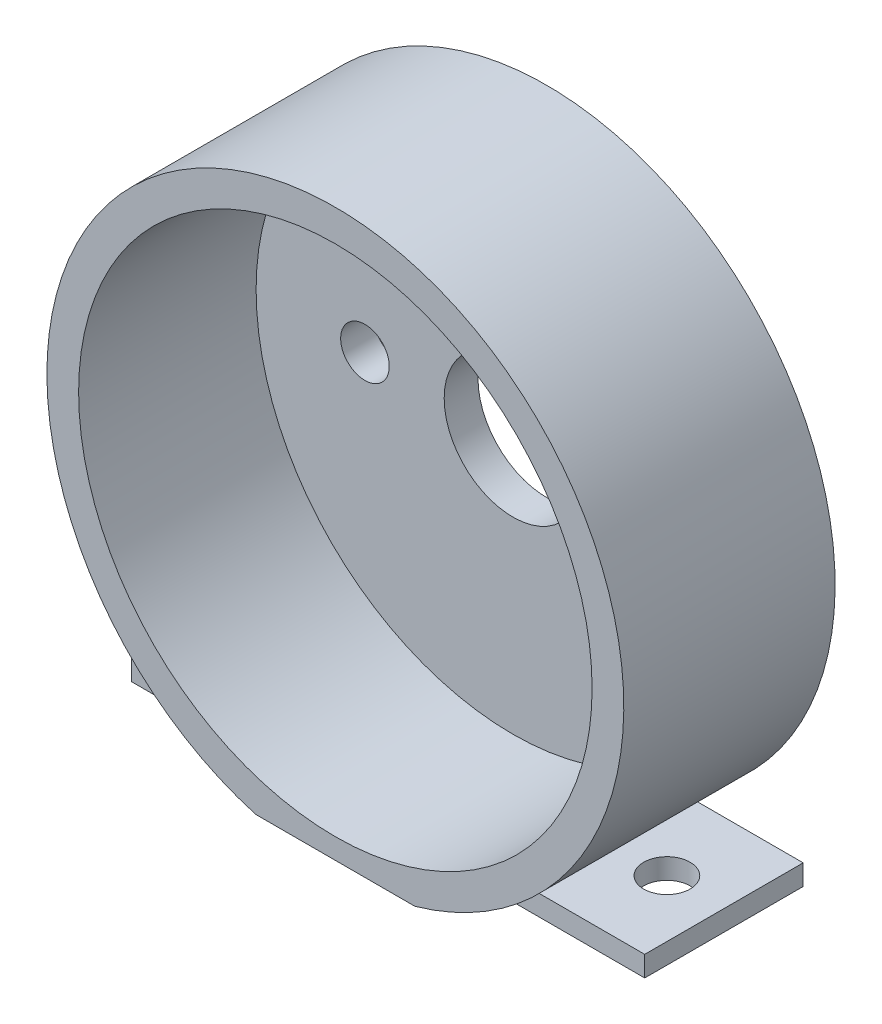
SolidWorks part; units mm, degrees
ref_plane "Front Plane" through (0, 0, 0) normal (0, 0, 1) x (1, 0, 0)
ref_plane "Top Plane" through (0, 0, 0) normal (0, 1, 0) x (1, 0, 0)
ref_plane "Right Plane" through (0, 0, 0) normal (1, 0, 0) x (0, 0, -1)
sketch "Sketch1" plane through (0, 0, 0) normal (0, 0, 1) x (1, 0, 0)
  circle A0 centre (0, 0) radius 12.15
  circle A1 centre (0, 0) radius 13.65
extrude "Boss-Extrude1" add sketch "Sketch1" along normal blind 10
sketch "Sketch2" plane through (0, 0, 10) normal (0, 0, 1) x (1, 0, 0)
  line L0 (5.5, 0) -> (-5.5, 0) construction
  line L1 (-9.25, 0) -> (9.25, 0) construction
  line L2 (0, -5.5) -> (0, 5.5) construction
  circle A0 centre (0, 0) radius 13.65
  circle A1 centre (0, 0) radius 4.25
  circle A2 centre (9.25, 0) radius 1.5
  circle A3 centre (-9.25, 0) radius 1.5
  point P10 (0, 0)
  dimension "D1" = 18.5
  dimension "D2" = 8.5
  dimension "D3" = 3
sketch "Sketch3" plane through (0, 0, 0) normal (0, 0, -1) x (-1, 0, 0)
  line L0 (-9.44, -13.65) -> (9.44, -13.65) construction
  line L2 (0, 5.5) -> (0, -5.5) construction
  line L3 (-6.2209, -12.15) -> (-12.14, -12.15)
  line L4 (-12.14, -12.15) -> (-12.14, -13.65)
  line L5 (-12.14, -13.65) -> (12.14, -13.65)
  line L6 (12.14, -12.15) -> (12.14, -13.65)
  line L7 (6.2209, -12.15) -> (12.14, -12.15)
  circle A1 centre (0, 0) radius 13.65 construction
  circle A3 centre (0, 0) radius 13.65
  point P2 (0, -13.65)
  point P13 (0, -13.65)
  circle M5 centre (0, 0) radius 13.65
  dimension "D1" = 18.88
  dimension "D2" = 2.7
  dimension "D3" = 1.5
extrude "Boss-Extrude3" add sketch "Sketch3" against normal blind 7.5 contours L4 L5 L3 M5 | L7 L5 L6 M5 region at (8.0338, -12.9777, 0) region at (-8.0338, -12.9777, 0)
sketch "Sketch5" plane through (0, -13.65, 0) normal (0, -1, 0) x (1, 0, 0)
  line L0 (-12.14, 7.5) -> (-12.14, 0) construction
  line L2 (-9.44, 0) -> (-9.44, 7.5) construction
  line L3 (14.7235, 0) -> (-14.7235, 0) construction
  line L4 (0, 7.5) -> (-12.14, 7.5) construction
  line L5 (0, -5.5) -> (0, 5.5) construction
  circle A0 centre (-9.44, 3.75) radius 1.1
  circle A2 centre (9.44, 3.75) radius 1.1
  point P14 (-9.44, 3.75)
  dimension "D1" = 2.7
  dimension "D3" = 2.2
extrude "Cut-Extrude1" cut sketch "Sketch5" against normal blind 1.5
sketch "Sketch6" plane through (0, 0, 0) normal (0, 0, -1) x (-1, 0, 0)
  line L1 (-12.14, -13.65) -> (12.14, -13.65)
  line L2 (-12.14, -13.65) -> (-12.14, -13.12)
  line L3 (-12.14, -13.12) -> (12.14, -13.12)
  line L4 (12.14, -13.65) -> (12.14, -13.12)
  dimension "D1" = 0.53
extrude "Cut-Extrude2" cut sketch "Sketch6" against normal through all
sketch "Sketch7" plane through (0, 0, 0) normal (0, 0, -1) x (-1, 0, 0)
  line L0 (9.25, 0) -> (-9.25, 0) construction
  line L1 (-7, 0) -> (7, 0) construction
  line L2 (0, 5.5) -> (0, -5.5) construction
  circle A0 centre (0, 0) radius 12.15
  circle A1 centre (-7, 0) radius 1.15
  circle A2 centre (7, 0) radius 1.15
  circle A3 centre (0, 0) radius 3.25
  point P6 (0, 0)
  dimension "D1" = 14
  dimension "D2" = 2.3
  dimension "D3" = 2.3
  dimension "D4" = 6.5
extrude "Boss-Extrude4" add sketch "Sketch7" against normal blind 1.6
